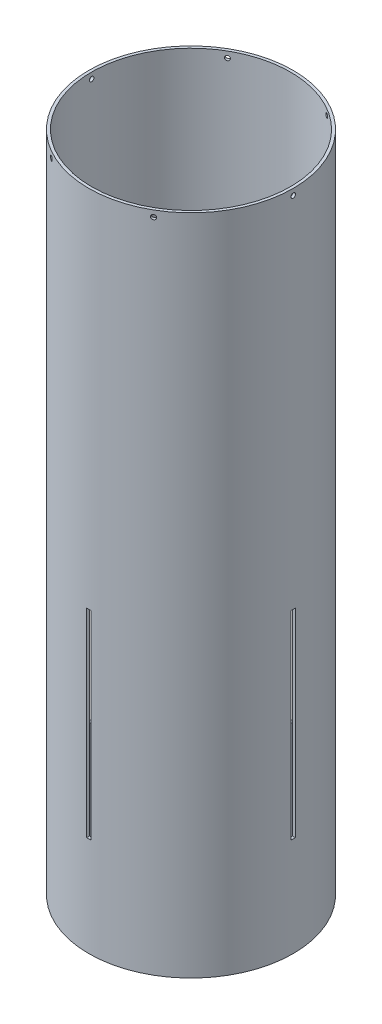
SolidWorks part; units mm, degrees
ref_plane "Front Plane" through (0, 0, 0) normal (0, 0, 1) x (1, 0, 0)
ref_plane "Top Plane" through (0, 0, 0) normal (0, 1, 0) x (1, 0, 0)
ref_plane "Right Plane" through (0, 0, 0) normal (1, 0, 0) x (0, 0, -1)
sketch "Sketch1" plane through (0, 0, 0) normal (0, 1, 0) x (1, 0, 0)
  circle A0 centre (0, 0) radius 76.2
  circle A1 centre (0, 0) radius 78.359
  dimension "D1" = 152.4
  dimension "D2" = 156.718
extrude "Boss-Extrude1" add sketch "Sketch1" along normal blind 508
ref_plane "Plane1" through (0, 0, 0) normal (0.7071, 0, 0.7071) x (0.7071, 0, -0.7071)
ref_axis "Axis1" through (0, 508, 0) along (0, -1, 0)
sketch "Sketch2" plane through (0, 0, 0) normal (1, 0, 0) x (0, 0, -1)
  line L0 (0, 0) -> (0, 76.2)
  line L1 (1.5875, 76.2) -> (-1.5875, 76.2)
  line L2 (1.5875, 76.2) -> (1.5875, 228.6)
  line L3 (1.5875, 228.6) -> (-1.5875, 228.6)
  line L4 (-1.5875, 76.2) -> (-1.5875, 228.6)
  line L5 (1.5875, 76.2) -> (-1.5875, 228.6) construction
  line L6 (1.5875, 228.6) -> (-1.5875, 76.2) construction
  line L7 (78.359, 508) -> (-78.359, 508) construction
  line L8 (78.359, 508) -> (-78.359, 508)
  line L9 (0, 508) -> (0, 503.2375)
  circle A0 centre (0, 503.2375) radius 1.75
  point P0 (0, 152.4)
  dimension "D4" = 3.5
  dimension "D1" = 3.175
  dimension "D2" = 152.4
  dimension "D3" = 76.2
  dimension "D5" = 4.7625
extrude "Cut-Extrude1" cut sketch "Sketch2" against normal through all contours L4 L1 L2 L3 region at (0, 152.4, 0)
pattern_circular "CirPattern1" count 4 over 360 about axis through (0, 0, 0) along (0, 1, 0) of "Cut-Extrude1" reverse direction yes
extrude "Cut-Extrude2" cut sketch "Sketch2<3>" against normal through all contours A0 region at (0, 502.0351, 1.2024)
sketch "Sketch2<3>" plane through (0, 0, 0) normal (1, 0, 0) x (0, 0, -1) same geometry as "Sketch2"
pattern_circular "CirPattern2" count 6 over 360 about axis through (0, 508, 0) along (0, -1, 0) of "Cut-Extrude2"
sketch "Sketch3" plane through (0, 0, 0) normal (0.7071, 0, 0.7071) x (0.7071, 0, -0.7071)
  line L0 (0, 0) -> (0, 127) construction
  circle A0 centre (0, 127) radius 3.175
  dimension "D1" = 6.35
  dimension "D2" = 127
extrude "Cut-Extrude3" cut sketch "Sketch3" against normal through all
equation "\"Aft_Lower_Length\"= 20in"
equation "\"D1@Boss-Extrude1\"=\"Aft_Lower_Length\""
equation "\"AB_Coupler_OD_Length\"= 2in"
equation "\"AB_Coupling_Section_Length\"= 0.375in"
equation "\"AB_Coupler_Length\"= \"AB_Coupler_OD_Length\" + \"AB_Coupling_Section_Length\" * 2"
equation "\"AB_Coupler_Num_Screws\"= 6"
equation "\"AB_Coupling_Screw_Diameter\"= 3.5mm"
equation "\"Aft_Upper_Length\"= \"Aft_Section_Length\" - \"Aft_Lower_Length\" - \"AB_Coupler_OD_Length\""
equation "\"Aft_Section_Length\"= 40in"
equation "\"D4@Sketch2\"=\"AB_Coupling_Screw_Diameter\""
equation "\"D5@Sketch2\"=\"AB_Coupling_Section_Length\"/2"
equation "\"D1@CirPattern2\"=\"AB_Coupler_Num_Screws\""
equation "\"Rail_Nut_From_Bottom\"= 5in"
equation "\"Rail_Nut_Diam\"= 0.25in"
equation "\"D1@Sketch3\"=\"Rail_Nut_Diam\""
equation "\"D2@Sketch3\"=\"Rail_Nut_From_Bottom\""
